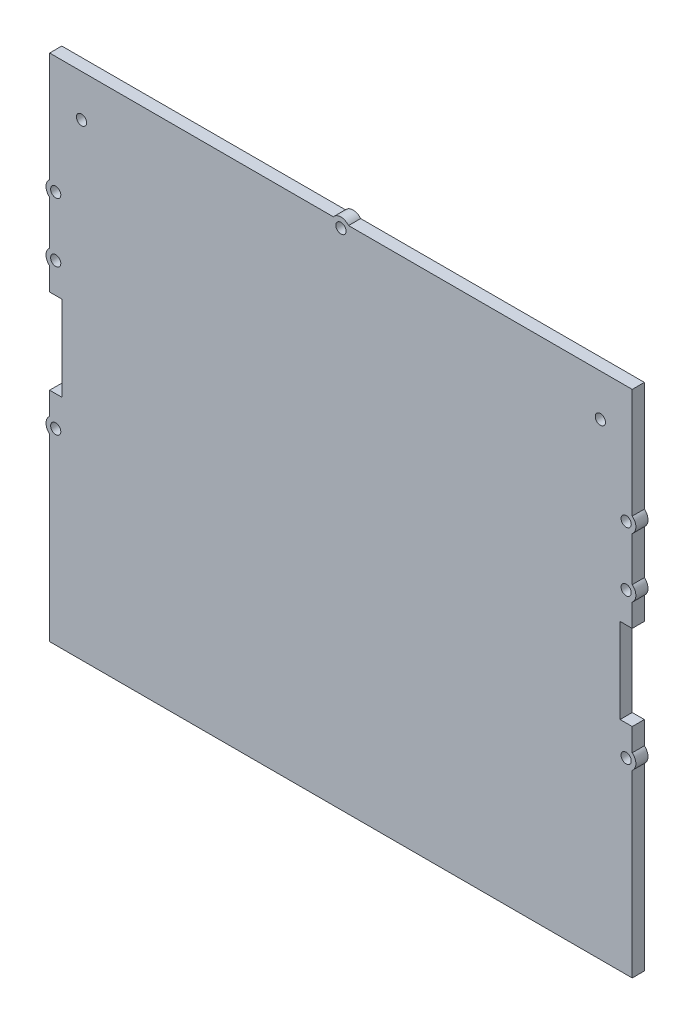
SolidWorks part; units mm, degrees
ref_plane "Front Plane" through (0, 0, 0) normal (0, 0, 1) x (1, 0, 0)
ref_plane "Top Plane" through (0, 0, 0) normal (0, 1, 0) x (1, 0, 0)
ref_plane "Right Plane" through (0, 0, 0) normal (1, 0, 0) x (0, 0, -1)
sketch "Sketch1" plane through (0, 0, 0) normal (0, 0, 1) x (1, 0, 0)
  line L1 (120, 105) -> (-120, 105)
  line L2 (120, 105) -> (120, 40)
  line L3 (120, -105) -> (-120, -105)
  line L4 (-120, 105) -> (-120, 40)
  line L5 (120, 105) -> (-120, -105) construction
  line L6 (120, -105) -> (-120, 105) construction
  line L12 (-120, -40) -> (-120, -105)
  line L13 (120, -40) -> (120, -105)
  line L14 (-120, 40) -> (-120, -40)
  line L15 (120, 40) -> (120, -40)
  point P0 (0, 0)
  point P12 (-120, 0)
  point P15 (120, 0)
  dimension "D1" = 240
  dimension "D2" = 210
extrude "Boss-Extrude1" add sketch "Sketch1" along normal blind 5
sketch "Sketch6" plane through (0, 0, 5) normal (0, 0, 1) x (1, 0, 0)
  line L3 (120, 40) -> (120, 105)
  line L5 (120, 66.5922) -> (120, 56.5922)
  line L8 (0, 102.5) -> (0, 83.8011) construction
  line L9 (-120, 100) -> (-120, 105)
  line L10 (-65, 100) -> (-120, 100)
  line L11 (-65, 105) -> (-65, 100)
  line L12 (-193.4408, 101.0702) -> (-189.5258, 105)
  line L13 (-130.8007, 38.6662) -> (-193.4408, 101.0702)
  line L14 (-98.4274, 71.162) -> (-130.8007, 38.6662)
  line L15 (-101.9696, 74.6908) -> (-98.4274, 71.162)
  line L16 (-105.0592, 71.5896) -> (-101.9696, 74.6908)
  line L17 (-112.5562, 64.0642) -> (-109.4667, 67.1654)
  line L66 (65, 105) -> (120, 105)
  line L68 (189.5258, 105) -> (120, 105)
  line L69 (120, 105) -> (120, 56.5922)
  line L72 (-109.014, 60.5353) -> (-112.5562, 64.0642)
  line L73 (-112.5428, 56.9931) -> (-109.014, 60.5353)
  line L78 (-116.0851, 60.522) -> (-112.5428, 56.9931)
  line L79 (-115, 40) -> (-120, 40)
  line L80 (-115, 105) -> (-115, 40)
  line L81 (-120, 105) -> (-115, 105)
  line L82 (-115, 66.5922) -> (-120, 66.5922)
  line L83 (-115, 56.5922) -> (-115, 66.5922)
  line L84 (-120, 56.5922) -> (-115, 56.5922)
  line L85 (-120, 105) -> (-120, 56.5922)
  line L86 (-189.5258, 105) -> (-120, 105)
  line L87 (-65, 105) -> (-120, 105)
  line L88 (-120, 56.5922) -> (-116.0851, 60.522)
  line L89 (-120, 66.5922) -> (-120, 56.5922)
  line L90 (-120, 40) -> (-120, 105)
  arc A3 (-109.4667, 67.1654) -> (-105.0592, 71.5896) centre (-105.4918, 67.6131) cw
extrude "Cut-Extrude1" cut sketch "Sketch6" against normal blind 5 rebuild error yes
sketch "Sketch7" plane through (0, 0, 5) normal (0, 0, 1) x (1, 0, 0)
  circle A0 centre (117.5, 56.66) radius 2.1 construction
  circle A1 centre (106.8639, 87.7263) radius 2.1 construction
  circle A2 centre (0, 102.5) radius 2.1 construction
  circle A3 centre (-117.5, 56.66) radius 2.1 construction
  circle A4 centre (-106.8639, 87.7263) radius 2.1 construction
  circle A5 centre (117.5, 56.66) radius 2.1
  circle A6 centre (106.8639, 87.7263) radius 2.1
  circle A7 centre (0, 102.5) radius 2.1
  circle A8 centre (-117.5, 56.66) radius 2.1
  circle A9 centre (-106.8639, 87.7263) radius 2.1
extrude "Cut-Extrude2" cut sketch "Sketch7" against normal blind 5
sketch "Sketch8" plane through (0, 0, 5) normal (0, 0, 1) x (1, 0, 0)
  line L0 (-120, 105) -> (-120, -105) construction
  line L1 (-120, 19.7147) -> (-115, 19.7147)
  line L2 (-120, 19.7147) -> (-120, -15.2853)
  line L3 (-120, -15.2853) -> (-115, -15.2853)
  line L4 (-115, 19.7147) -> (-115, -15.2853)
  line L5 (-120, 44.7147) -> (-115, 44.7147) construction
  line L6 (0, 73.4459) -> (0, 23.7155) construction
  line L7 (115, 19.7147) -> (115, -15.2853)
  line L8 (120, -15.2853) -> (115, -15.2853)
  line L9 (120, 19.7147) -> (120, -15.2853)
  line L10 (120, 19.7147) -> (115, 19.7147)
  circle A0 centre (-117.5, 32.2147) radius 2.1
  circle A1 centre (-117.5, -27.7853) radius 2.1
  circle A2 centre (117.5, -27.7853) radius 2.1
  circle A3 centre (117.5, 32.2147) radius 2.1
  dimension "D4" = 4.2
  dimension "D5" = 2.5
  dimension "D6" = 12.5
  dimension "D7" = 12.5
  dimension "D8" = 4.2
  dimension "D9" = 2.5
  dimension "D1" = 5
  dimension "D2" = 25
  dimension "D3" = 35
extrude "Cut-Extrude3" cut sketch "Sketch8" against normal blind 5
sketch "Sketch9" plane through (0, 0, 5) normal (0, 0, 1) x (1, 0, 0)
  line L0 (120, 59.7825) -> (120, 53.5375)
  line L1 (120, 54.7147) -> (120, 64.7147) construction
  line L2 (120, 35.3372) -> (120, 29.0922)
  line L3 (120, 19.7147) -> (120, 105) construction
  line L4 (120, -24.6628) -> (120, -30.9078)
  line L5 (120, -105) -> (120, -15.2853) construction
  line L6 (-3.1225, 105) -> (3.1225, 105)
  line L7 (120, 105) -> (-120, 105) construction
  line L8 (0, 102.5) -> (0, 78.5938) construction
  line L9 (-120, -24.6628) -> (-120, -30.9078)
  line L10 (-120, 35.3372) -> (-120, 29.0922)
  line L11 (-120, 59.7825) -> (-120, 53.5375)
  arc A0 (120, 53.5375) -> (120, 59.7825) centre (117.5, 56.66) ccw
  arc A1 (120, 29.0922) -> (120, 35.3372) centre (117.5, 32.2147) ccw
  arc A2 (120, -30.9078) -> (120, -24.6628) centre (117.5, -27.7853) ccw
  arc A3 (3.1225, 105) -> (-3.1225, 105) centre (0, 102.5) ccw
  arc A4 (-120, -30.9078) -> (-120, -24.6628) centre (-117.5, -27.7853) cw
  arc A5 (-120, 29.0922) -> (-120, 35.3372) centre (-117.5, 32.2147) cw
  arc A6 (-120, 53.5375) -> (-120, 59.7825) centre (-117.5, 56.66) cw
  dimension "D1" = 8
  dimension "D2" = 8
  dimension "D3" = 8
extrude "Boss-Extrude2" add sketch "Sketch9" against normal blind 5
